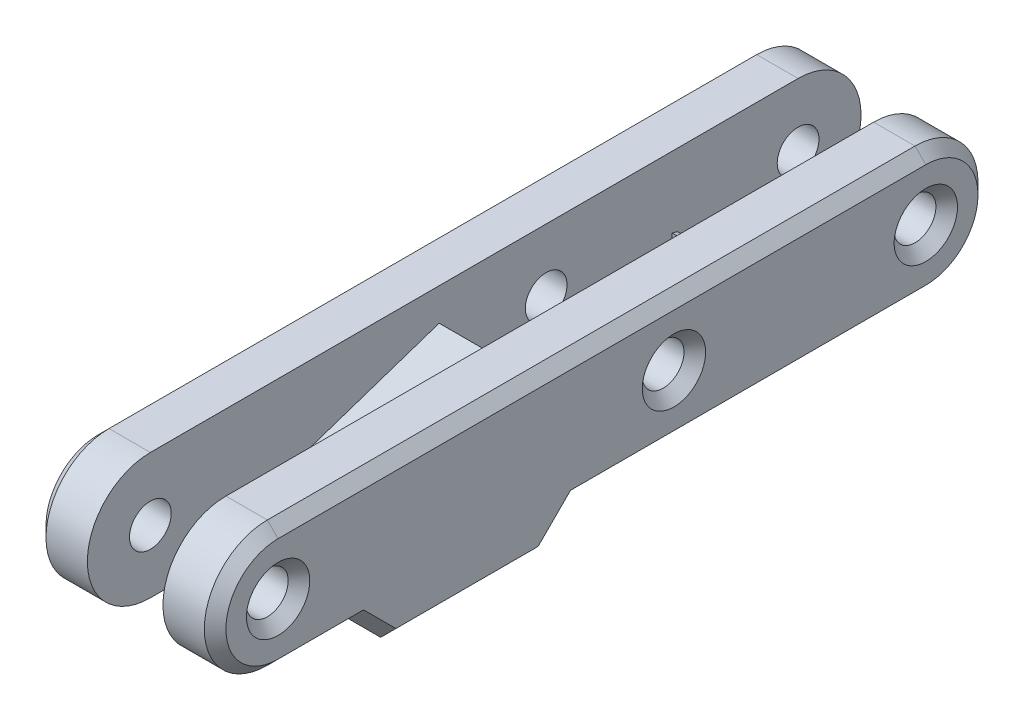
SolidWorks part; units mm, degrees
note: The reader was unsure of these and kept them because the rebuilt part matched: shared geometry of "草图2<4>".
material "环氧树脂,未充填"
ref_plane "前视基准面" through (0, 0, 0) normal (0, 0, 1) x (1, 0, 0)
ref_plane "上视基准面" through (0, 0, 0) normal (0, 1, 0) x (1, 0, 0)
ref_plane "右视基准面" through (0, 0, 0) normal (1, 0, 0) x (0, 0, -1)
other "Configuration Table"
sketch "草图1" plane through (0, 0, 0) normal (1, 0, 0) x (0, 0, -1)
  line L0 (-18, 0) -> (18, 0) construction
  line L1 (18, 0) -> (4, 0) construction
  line L2 (-18, 0) -> (18, 0) construction
  line L3 (-18, 3.5) -> (18, 3.5)
  line L4 (-18, -3.5) -> (18, -3.5)
  circle A0 centre (18, 0) radius 1.16
  circle A1 centre (4, 0) radius 1.16
  circle A2 centre (-18, 0) radius 1.16
  arc A3 (-18, 3.5) -> (-18, -3.5) centre (-18, 0) ccw
  arc A4 (18, -3.5) -> (18, 3.5) centre (18, 0) ccw
  point P4 (0, 0)
  point P10 (0, 0)
  dimension "D4" = 3.5
  dimension "D6" = 2.32
  dimension "D1" = 22
  dimension "D2" = 14
extrude "凸台-拉伸1" add sketch "草图1" along normal mid plane 10
sketch "草图2" plane through (0, 0, 0) normal (1, 0, 0) x (0, 0, -1)
  line L0 (-4.624, 0.7974) -> (-44190.4435, -14829.0378) construction
  line L2 (18, 3.5) -> (-18, 3.5) construction
  line L3 (0.5, -3.5) -> (0.5, 49996.5) construction
  line L7 (-18, -3.5) -> (18, -3.5)
  line L8 (18, 3.5) -> (-18, 3.5)
  line L9 (-18, -3.5) -> (18, -3.5)
  line L10 (18, 3.5) -> (-18, 3.5)
  line L11 (0.5, -3.5) -> (-17.4283, -3.5)
  line L12 (-18, -3.5) -> (18, -3.5) construction
  line L13 (-17.4283, -3.5) -> (-1.5, 1.8459)
  line L14 (-1.5, 1.8459) -> (-1.5, -3.5)
  line L15 (18, 0) -> (4, 0) construction
  line L19 (11, 0) -> (11, -3.5)
  line L20 (11, -3.5) -> (13, -3.5)
  line L21 (13, -3.5) -> (11, 0)
  circle A0 centre (-18, 0) radius 3.5
  circle A1 centre (4, 0) radius 3.5
  circle A2 centre (18, 0) radius 3.5
  arc A4 (-18, 3.5) -> (-18, -3.5) centre (-18, 0) ccw
  arc A5 (18, -3.5) -> (18, 3.5) centre (18, 0) ccw
  arc A6 (-18, 3.5) -> (-18, -3.5) centre (-18, 0) ccw
  arc A7 (18, -3.5) -> (18, 3.5) centre (18, 0) ccw
  point P30 (11, 0)
  dimension "D2" = 2
  dimension "D3" = 2
  dimension "D1" = 0
extrude "切除-拉伸1" cut sketch "草图2" against normal mid plane 4.2 contours L10 A6 L9 A7
extrude "凸台-拉伸2" add sketch "草图2<4>" along normal mid plane 5
sketch "草图2<4>" plane through (0, 0, 0) normal (1, 0, 0) x (0, 0, -1) same geometry as "草图2"
sketch "草图3" plane through (0, 0, 0) normal (1, 0, 0) x (0, 0, -1)
  line L1 (-11.7, -5.3) -> (-3.3, -5.3)
  line L2 (-3.3, -5.3) -> (-1.5, -3.5)
  line L7 (-1.5, -3.5) -> (11, -3.5)
  line L8 (18, 3.5) -> (-18, 3.5)
  line L12 (-1.5, -3.5) -> (11, -3.5) construction
  line L13 (18, 3.5) -> (-18, 3.5) construction
  line L18 (-1.5, -3.5) -> (-13.5, -3.5)
  line L19 (-18, -3.5) -> (18, -3.5) construction
  line L20 (-13.5, -3.5) -> (-11.7, -5.3)
  line L26 (-17.4283, -3.5) -> (-1.5, 1.8459)
  line L27 (-17.4283, -3.5) -> (-1.5, 1.8459)
  line L28 (-1.5, 1.8459) -> (-1.5, -3.5)
  line L29 (-1.5, 1.8459) -> (-1.5, -3.5)
  line L30 (-18, -3.5) -> (-17.4283, -3.5)
  line L31 (-18, -3.5) -> (-17.4283, -3.5)
  line L32 (11, 0) -> (13, -3.5)
  line L33 (11, 0) -> (13, -3.5)
  line L34 (13, -3.5) -> (18, -3.5)
  line L35 (13, -3.5) -> (18, -3.5)
  line L36 (11, -3.5) -> (11, 0)
  line L37 (11, -3.5) -> (11, 0)
  arc A2 (18, -3.5) -> (18, 3.5) centre (18, 0) ccw
  arc A3 (-18, 3.5) -> (-18, -3.5) centre (-18, 0) ccw
  arc A4 (18, -3.5) -> (18, 3.5) centre (18, 0) ccw construction
  arc A5 (-18, 3.5) -> (-18, -3.5) centre (-18, 0) ccw construction
  point P1 (0, 0)
  dimension "D2" = 1.8
  dimension "D3" = 45
  dimension "D4" = 12
  dimension "D1" = 0
extrude "凸台-拉伸3" add sketch "草图3" along normal mid plane 10 contours L18 L20 L1 L2
chamfer "倒角2" distance 0.6 angle 45 27 edges at (-5, 0, 21.5) (-5, -3.5, 15.75) (-5, 0, -21.5) (-5, 3.5, 0) (-5, 0, -19.16) (-5, 0, -5.16) (-5, 0, 16.84) (0, 1.8459, 1.5) (0, -3.5, 17.4283) (5, 0, -19.16) (5, 0, -5.16) (5, 0, 21.5) (5, -3.5, 15.75) (5, 0, -21.5) (5, 3.5, 0) (5, 0, 16.84) (0, -3.5, -11) (0, -3.5, -13) (0, 0, -11) (5, -3.5, -8.25) (-5, -3.5, -8.25) (-5, -4.4, 12.6) (-5, -5.3, 7.5) (-5, -4.4, 2.4) (5, -4.4, 12.6) (5, -5.3, 7.5) (5, -4.4, 2.4)
